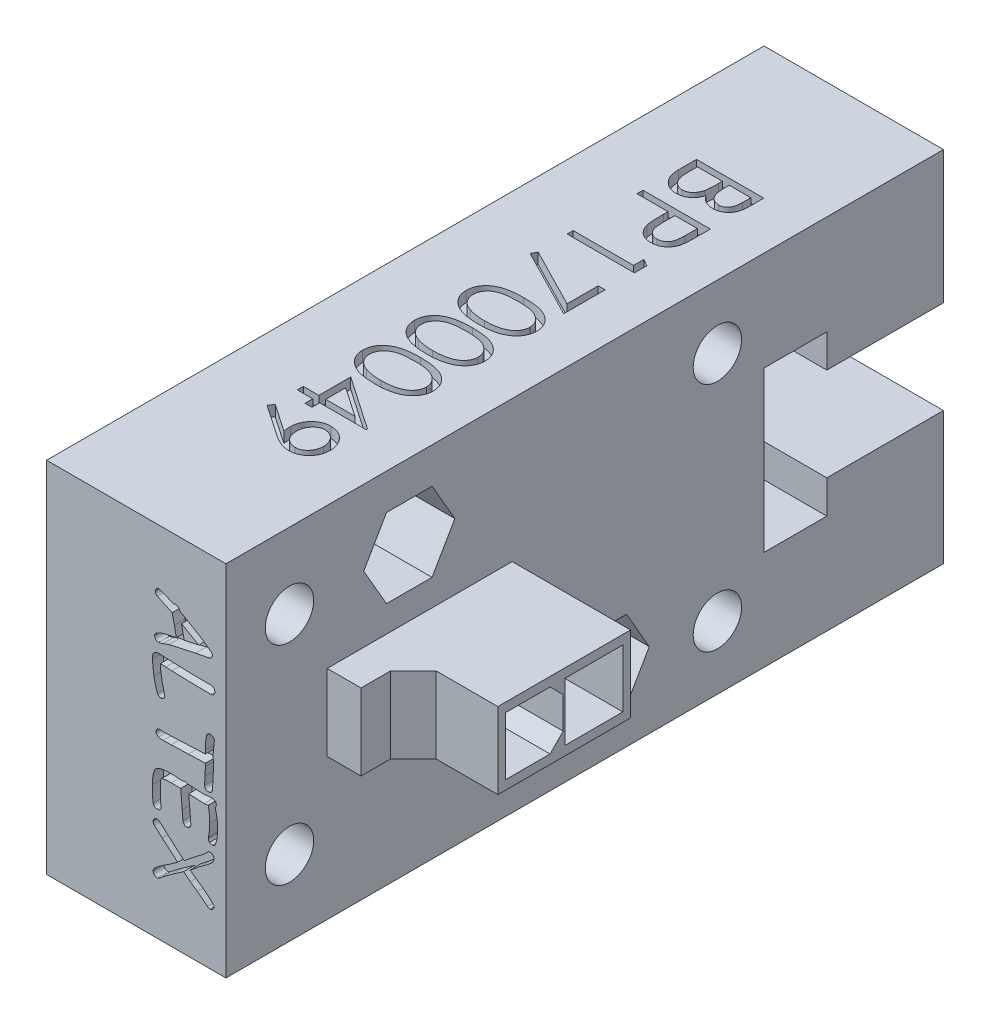
SolidWorks part; units mm, degrees
ref_plane "Front Plane" through (0, 0, 0) normal (1, 0, 0) x (0, 1, 0)
ref_plane "Top Plane" through (0, 0, 0) normal (0, 0, 1) x (0, 1, 0)
ref_plane "Right Plane" through (0, 0, 0) normal (0, 1, 0) x (-1, 0, 0)
sketch "Sketch1" plane through (0, 0, 0) normal (1, 0, 0) x (0, 1, 0)
  line L1 (-12.7, -25.4) -> (12.7, -25.4)
  line L2 (-12.7, -25.4) -> (-12.7, 25.4)
  line L3 (-12.7, 25.4) -> (12.7, 25.4)
  line L4 (12.7, -25.4) -> (12.7, 25.4)
  line L5 (-12.7, -25.4) -> (12.7, 25.4) construction
  line L6 (-12.7, 25.4) -> (12.7, -25.4) construction
  point P0 (0, 0)
  dimension "D1" = 25.4
  dimension "D2" = 50.8
extrude "Boss-Extrude1" add sketch "Sketch1" along normal blind 12.7
sketch "Sketch2" plane through (12.7, 0, 0) normal (1, 0, 0) x (0, 1, 0)
  line L0 (0, -25.4) -> (0, -12.7) construction
  line L1 (-12.7, -25.4) -> (12.7, -25.4) construction
  line L2 (3.302, -17.145) -> (5.6515, -17.145)
  line L3 (-5.6515, -12.7) -> (5.6515, -12.7)
  line L4 (-5.6515, -12.7) -> (-5.6515, -17.145)
  line L5 (-5.6515, -17.145) -> (-3.302, -17.145)
  line L6 (5.6515, -12.7) -> (5.6515, -17.145)
  line L8 (-3.302, -17.145) -> (-3.302, -25.4)
  line L9 (-3.302, -25.4) -> (3.302, -25.4)
  line L10 (3.302, -17.145) -> (3.302, -25.4)
  dimension "D1" = 12.7
  dimension "D2" = 6.604
  dimension "D3" = 3.302
  dimension "D4" = 4.445
  dimension "D5" = 5.6515
  dimension "D6" = 11.303
extrude "Cut-Extrude1" cut sketch "Sketch2" against normal up to vertex (12.7 mm away) up to point (0, 12.7, -25.4)
sketch "Sketch3" plane through (0, 0, 0) normal (-1, 0, 0) x (0, -1, 0)
  circle A0 centre (0, 12.107) radius 1.0287
  circle A1 centre (0, 7.907) radius 1.0287
  dimension "D1" = 2.0574
  dimension "D2" = 2.0574
extrude "Cut-Extrude2" cut sketch "Sketch3" against normal up to vertex (12.7 mm away) up to point (12.7, 12.7, 25.4)
sketch "Sketch6" plane through (0, 0, 25.4) normal (0, 0, 1) x (1, 0, 0)
  line L0 (7.7518, 12.7) -> (7.7518, -12.7) construction
  text T0 "ALTEX" font "Comic Sans MS" height in points 16
extrude "Cut-Extrude4" cut sketch "Sketch6" against normal blind 0.762
sketch "Sketch7" plane through (0, -12.7, 0) normal (0, -1, 0) x (1, 0, 0)
  line L0 (6.35, 25.4) -> (6.35, -25.4) construction
  line L1 (12.7, -25.4) -> (0, -25.4) construction
  line L2 (12.7, 25.4) -> (0, 25.4) construction
  text T0 "39-01-2020" font "Century Gothic" height in points 18
extrude "Cut-Extrude5" cut sketch "Sketch7" against normal blind 0.762
sketch "Sketch8" plane through (0, 12.7, 0) normal (0, 1, 0) x (-1, 0, 0)
  line L0 (-4.5604, -25.4) -> (-4.5604, 25.4) construction
  line L1 (-12.7, -25.4) -> (0, -25.4) construction
  line L2 (-12.7, 25.4) -> (0, 25.4) construction
  text T0 "BP1700049" font "Century Gothic" height in points 18
extrude "Cut-Extrude6" cut sketch "Sketch8" against normal blind 0.762
sketch "Sketch9" plane through (0, 0, 25.4) normal (0, 0, 1) x (1, 0, 0)
  line L0 (1.2659, 12.7) -> (1.2659, -12.7) construction
  line L1 (12.7, 12.7) -> (0, 12.7) construction
  line L2 (12.7, -12.7) -> (0, -12.7) construction
  text T0 "PCHI#10" font "Comic Sans MS" height in points 14
sketch "Sketch10" plane through (12.7, 0, 0) normal (1, 0, 0) x (0, 1, 0)
  line L0 (-12.7, 25.4) -> (-12.7, -25.4) construction
  line L1 (-7.366, 17.6775) -> (-4.572, 19.2907)
  line L2 (-4.572, 19.2907) -> (-4.572, 22.5169)
  line L3 (-4.572, 22.5169) -> (-7.366, 24.13)
  line L4 (-7.366, 24.13) -> (-10.16, 22.5169)
  line L5 (-10.16, 22.5169) -> (-10.16, 19.2907)
  line L6 (-10.16, 19.2907) -> (-7.366, 17.6775)
  line L7 (7.366, 17.6775) -> (10.16, 19.2907)
  line L8 (10.16, 19.2907) -> (10.16, 22.5169)
  line L9 (10.16, 22.5169) -> (7.366, 24.13)
  line L10 (7.366, 24.13) -> (4.572, 22.5169)
  line L11 (4.572, 22.5169) -> (4.572, 19.2907)
  line L12 (4.572, 19.2907) -> (7.366, 17.6775)
  line L13 (12.7, -25.4) -> (12.7, 25.4) construction
  line L14 (12.7, 25.4) -> (-12.7, 25.4) construction
  line L15 (-12.7, -25.4) -> (-3.302, -25.4) construction
  line L16 (-4.9775, -9.398) -> (-6.5907, -6.604)
  line L17 (-6.5907, -6.604) -> (-9.8169, -6.604)
  line L18 (-9.8169, -6.604) -> (-11.43, -9.398)
  line L19 (-11.43, -9.398) -> (-9.8169, -12.192)
  line L20 (-9.8169, -12.192) -> (-6.5907, -12.192)
  line L21 (-6.5907, -12.192) -> (-4.9775, -9.398)
  line L22 (11.43, -9.398) -> (9.8169, -6.604)
  line L23 (9.8169, -6.604) -> (6.5907, -6.604)
  line L24 (6.5907, -6.604) -> (4.9775, -9.398)
  line L25 (4.9775, -9.398) -> (6.5907, -12.192)
  line L26 (6.5907, -12.192) -> (9.8169, -12.192)
  line L27 (9.8169, -12.192) -> (11.43, -9.398)
  circle A0 centre (-7.366, 20.9038) radius 2.794 construction
  circle A1 centre (7.366, 20.9038) radius 2.794 construction
  circle A2 centre (-8.2038, -9.398) radius 2.794 construction
  circle A3 centre (8.2038, -9.398) radius 2.794 construction
  dimension "D1" = 5.588
  dimension "D2" = 5.588
  dimension "D3" = 2.54
  dimension "D4" = 2.54
  dimension "D5" = 1.27
  dimension "D6" = 1.27
  dimension "D7" = 5.588
  dimension "D8" = 5.588
  dimension "D9" = 1.27
  dimension "D10" = 1.27
  dimension "D11" = 13.208
extrude "Cut-Extrude8" cut sketch "Sketch10" against normal blind 2.54
sketch "Sketch11" plane through (0, 0, 0) normal (-1, 0, 0) x (0, -1, 0)
  line L0 (-7.366, 24.13) -> (-7.366, 17.6775) construction
  line L1 (-7.366, 17.6775) -> (7.366, 24.13) construction
  line L2 (7.366, 24.13) -> (7.366, 17.6775) construction
  line L3 (7.366, 17.6775) -> (4.9775, -9.398) construction
  line L4 (4.9775, -9.398) -> (11.43, -9.398) construction
  line L5 (11.43, -9.398) -> (-9.8169, -6.604) construction
  line L6 (-9.8169, -6.604) -> (-6.5907, -12.192) construction
  line L8 (-7.366, 24.13) -> (-10.16, 22.5169)
  line L9 (-10.16, 22.5169) -> (-10.16, 19.2907)
  line L10 (-10.16, 19.2907) -> (-7.366, 17.6775)
  line L11 (-7.366, 17.6775) -> (-4.572, 19.2907)
  line L12 (-4.572, 19.2907) -> (-4.572, 22.5169)
  line L13 (-4.572, 22.5169) -> (-7.366, 24.13)
  line L14 (7.366, 17.6775) -> (10.16, 19.2907)
  line L15 (10.16, 19.2907) -> (10.16, 22.5169)
  line L16 (10.16, 22.5169) -> (7.366, 24.13)
  line L17 (7.366, 24.13) -> (4.572, 22.5169)
  line L18 (4.572, 22.5169) -> (4.572, 19.2907)
  line L19 (4.572, 19.2907) -> (7.366, 17.6775)
  line L20 (11.43, -9.398) -> (9.8169, -6.604)
  line L21 (9.8169, -6.604) -> (6.5907, -6.604)
  line L22 (6.5907, -6.604) -> (4.9775, -9.398)
  line L23 (4.9775, -9.398) -> (6.5907, -12.192)
  line L24 (6.5907, -12.192) -> (9.8169, -12.192)
  line L25 (9.8169, -12.192) -> (11.43, -9.398)
  line L26 (-9.8169, -6.604) -> (-11.43, -9.398)
  line L27 (-11.43, -9.398) -> (-9.8169, -12.192)
  line L28 (-9.8169, -12.192) -> (-6.5907, -12.192)
  line L29 (-6.5907, -12.192) -> (-4.9775, -9.398)
  line L30 (-4.9775, -9.398) -> (-6.5907, -6.604)
  line L31 (-6.5907, -6.604) -> (-9.8169, -6.604)
  circle A0 centre (-8.2038, -9.398) radius 1.651 construction
  circle A1 centre (8.2038, -9.398) radius 1.651 construction
  circle A2 centre (7.366, 20.9038) radius 1.651 construction
  circle A3 centre (-7.366, 20.9038) radius 1.7145 construction
  circle A4 centre (-7.366, 20.9038) radius 2.794 construction
  circle A5 centre (7.366, 20.9038) radius 2.794 construction
  circle A6 centre (8.2038, -9.398) radius 2.794 construction
  circle A7 centre (-8.2038, -9.398) radius 2.794 construction
  dimension "D1" = 3.429
  dimension "D2" = 3.302
extrude "Cut-Extrude9" cut sketch "Sketch11" against normal blind 2.54
sketch "Sketch12" plane through (2.54, 0, 0) normal (-1, 0, 0) x (0, -1, 0)
  line L0 (-7.366, 17.6775) -> (-7.366, 24.13) construction
  line L1 (-7.366, 24.13) -> (7.366, 24.13) construction
  line L2 (7.366, 24.13) -> (7.366, 17.6775) construction
  line L3 (7.366, 17.6775) -> (9.8169, -6.604) construction
  line L4 (9.8169, -6.604) -> (6.5907, -12.192) construction
  line L5 (6.5907, -12.192) -> (-6.5907, -12.192) construction
  line L6 (-6.5907, -12.192) -> (-9.8169, -6.604) construction
  circle A0 centre (-8.2038, -9.398) radius 1.7145
  circle A1 centre (8.2038, -9.398) radius 1.7145
  circle A2 centre (7.366, 20.9038) radius 1.7145
  circle A3 centre (-7.366, 20.9038) radius 1.7145
  dimension "D1" = 3.429
extrude "Cut-Extrude10" cut sketch "Sketch12" against normal up to vertex (7.62 mm away) up to point (10.16, -4.572, 19.2907)
sketch "Sketch13" plane through (12.7, 0, 0) normal (1, 0, 0) x (0, 1, 0)
  line L0 (1.0596, 10.0542) -> (1.9032, 10.8978)
  line L1 (-1.9032, 13.8352) -> (1.9032, 13.8352)
  line L2 (-1.9032, 13.8352) -> (-1.9032, 10.8978)
  line L3 (-1.0596, 10.0542) -> (1.0596, 10.0542)
  line L4 (1.9032, 13.8352) -> (1.9032, 10.8978)
  line L5 (-1.9032, 9.6098) -> (1.9032, 9.6098)
  line L6 (-1.9032, 9.6098) -> (-1.9032, 5.8288)
  line L7 (-1.9032, 5.8288) -> (1.9032, 5.8288)
  line L8 (1.9032, 9.6098) -> (1.9032, 5.8288)
  line L9 (-1.0596, 10.0542) -> (-1.9032, 10.8978)
  line L10 (1.7, 13.632) -> (3.3632, 13.632) construction
  line L11 (1.7, 13.632) -> (1.7, 12.5497) construction
  line L12 (1.7, 13.632) -> (1.7, 10.982) construction
  line L13 (1.7, 9.432) -> (3.2737, 9.432) construction
  line L14 (1.7, 9.432) -> (1.7, 6.7746) construction
  line L15 (1.7, 9.432) -> (1.7, 6.032) construction
  line L16 (0.95, 10.232) -> (2.5714, 10.232) construction
  line L17 (-1.7, 10.982) -> (-1.7, 9.7205) construction
  line L19 (1.7, 6.032) -> (-1.7, 6.032) construction
  line L20 (-7.4385, 14.732) -> (5.1104, 14.732) construction
  line L21 (-3.1732, 14.5288) -> (3.1732, 14.5288)
  line L22 (-3.1732, 14.5288) -> (-3.1732, 5.3238)
  line L23 (-3.1732, 5.3238) -> (3.1732, 5.3238)
  line L24 (3.1732, 14.5288) -> (3.1732, 5.3238)
  line L25 (1.5, 14.732) -> (-1.5, 14.732) construction
  dimension "D1" = 45
  dimension "D2" = 45
  dimension "D3" = 0.2032
  dimension "D4" = 0.1778
  dimension "D5" = 0.2032
  dimension "D6" = 0.1778
  dimension "D7" = 0.2032
  dimension "D8" = 0.2032
  dimension "D9" = 0.2032
  dimension "D10" = 0.2032
  dimension "D11" = 0.2032
  dimension "D12" = 1.27
  dimension "D13" = 1.27
extrude "Boss-Extrude2" add sketch "Sketch13" along normal blind 8.382
sketch "Sketch14" plane through (0, -3.1732, 0) normal (0, -1, 0) x (1, 0, 0)
  line L0 (20.3329, 18.232) -> (13.3, 18.232) construction
  line L1 (28.6, 18.232) -> (16, 18.232) construction
  line L2 (15.3, 17.532) -> (15.3, 12.9236) construction
  line L3 (16.8, 14.732) -> (13.3, 18.232) construction
  line L6 (15.0968, 18.232) -> (12.7, 18.232)
  line L7 (15.0968, 18.232) -> (15.0968, 16.1478)
  line L9 (12.7, 18.232) -> (12.7, 14.5288)
  line L10 (21.082, 14.5288) -> (12.7, 14.5288) construction
  line L11 (16.7158, 14.5288) -> (15.0968, 16.1478)
  line L12 (12.7, 14.5288) -> (16.7158, 14.5288)
  dimension "D1" = 0.2032
  dimension "D2" = 0.2032
extrude "Boss-Extrude3" add sketch "Sketch14" against normal up to vertex (6.3464 mm away) up to point (21.082, 3.1732, 14.5288)
sketch "Sketch15" plane through (21.082, 0, 0) normal (1, 0, 0) x (0, 1, 0)
  line L0 (3.1732, 18.232) -> (-3.1732, 18.232) construction
  line L1 (-3.1732, 5.3238) -> (-2.7, 5.3238)
  line L2 (-3.1732, 5.3238) -> (-3.1732, 18.232)
  line L3 (-3.1732, 18.232) -> (-2.7, 18.232)
  line L4 (-2.7, 5.3238) -> (-2.7, 18.232)
  line L5 (2.7, 9.5624) -> (2.7, 4.4692) construction
  line L6 (2.7, 18.232) -> (3.1732, 18.232)
  line L7 (2.7, 18.232) -> (2.7, 5.3238)
  line L8 (2.7, 5.3238) -> (3.1732, 5.3238)
  line L9 (3.1732, 18.232) -> (3.1732, 5.3238)
  line L10 (2.7, 4.132) -> (2.7, 14.732) construction
  line L11 (-2.7, 9.432) -> (-2.7, 4.4692) construction
  line L12 (-2.7, 4.132) -> (-2.7, 14.732) construction
extrude "Cut-Extrude11" cut sketch "Sketch15" against normal up to vertex (8.382 mm away) up to point (12.7, 12.7, 25.4)
sketch "Sketch16" plane through (21.082, 0, 0) normal (1, 0, 0) x (0, 1, 0)
  line L1 (-2.7, 5.3238) -> (2.7, 5.3238)
  line L2 (-2.7, 5.3238) -> (-2.7, 5.132)
  line L3 (-2.7, 5.132) -> (2.7, 5.132)
  line L4 (2.7, 5.3238) -> (2.7, 5.132)
extrude "Boss-Extrude4" add sketch "Sketch16" against normal up to vertex (8.382 mm away) up to point (12.7, -2.7, 5.3238)
sketch "Sketch17" plane through (12.7, 0, 0) normal (1, 0, 0) x (0, 1, 0)
  line L12 (1.9794, 13.9114) -> (-1.9794, 13.9114)
  line L13 (-1.9794, 13.9114) -> (-1.9794, 10.8663)
  line L14 (-1.9794, 10.8663) -> (-1.0911, 9.978)
  line L15 (-1.0911, 9.978) -> (1.0911, 9.978)
  line L16 (1.0911, 9.978) -> (1.9794, 10.8663)
  line L17 (1.9794, 10.8663) -> (1.9794, 13.9114)
  line L18 (1.9794, 13.9114) -> (-1.9794, 13.9114)
  line L19 (-1.9794, 13.9114) -> (-1.9794, 10.8663)
  line L20 (-1.9794, 10.8663) -> (-1.0911, 9.978)
  line L21 (-1.0911, 9.978) -> (1.0911, 9.978)
  line L22 (1.0911, 9.978) -> (1.9794, 10.8663)
  line L23 (1.9794, 10.8663) -> (1.9794, 13.9114)
  line L26 (1.9794, 9.686) -> (-1.9794, 9.686)
  line L27 (-1.9794, 9.686) -> (-1.9794, 5.7526)
  line L28 (-1.9794, 5.7526) -> (1.9794, 5.7526)
  line L29 (1.9794, 5.7526) -> (1.9794, 9.686)
  line L30 (1.9794, 9.686) -> (-1.9794, 9.686)
  line L31 (-1.9794, 9.686) -> (-1.9794, 5.7526)
  line L32 (-1.9794, 5.7526) -> (1.9794, 5.7526)
  line L33 (1.9794, 5.7526) -> (1.9794, 9.686)
  dimension "D1" = 0.0762
  dimension "D2" = 0.0762
extrude "Cut-Extrude12" cut sketch "Sketch17" along normal up to vertex (8.382 mm away) up to point (21.082, -2.7, 5.132)
sketch "Sketch18" plane through (10.16, 0, 0) normal (1, 0, 0) x (0, 1, 0)
  line L0 (9.8169, -12.192) -> (11.43, -9.398) construction
  line L1 (11.43, -9.398) -> (9.8169, -6.604) construction
  line L2 (9.8169, -6.604) -> (6.5907, -6.604) construction
  line L3 (6.5907, -6.604) -> (4.9775, -9.398) construction
  line L4 (4.9775, -9.398) -> (6.5907, -12.192) construction
  line L5 (6.5907, -12.192) -> (9.8169, -12.192) construction
  line L6 (-10.16, 19.2907) -> (-7.366, 17.6775)
  line L7 (-7.366, 17.6775) -> (-4.572, 19.2907)
  line L8 (-4.572, 19.2907) -> (-4.572, 22.5169)
  line L9 (-4.572, 22.5169) -> (-7.366, 24.13)
  line L10 (-7.366, 24.13) -> (-10.16, 22.5169)
  line L11 (-10.16, 22.5169) -> (-10.16, 19.2907)
  line L12 (-10.16, 19.2907) -> (-7.366, 17.6775)
  line L13 (-7.366, 17.6775) -> (-4.572, 19.2907)
  line L14 (-4.572, 19.2907) -> (-4.572, 22.5169)
  line L15 (-4.572, 22.5169) -> (-7.366, 24.13)
  line L16 (-7.366, 24.13) -> (-10.16, 22.5169)
  line L17 (-10.16, 22.5169) -> (-10.16, 19.2907)
  line L18 (4.572, 19.2907) -> (7.366, 17.6775)
  line L19 (7.366, 17.6775) -> (10.16, 19.2907)
  line L20 (10.16, 19.2907) -> (10.16, 22.5169)
  line L21 (10.16, 22.5169) -> (7.366, 24.13)
  line L22 (7.366, 24.13) -> (4.572, 22.5169)
  line L23 (4.572, 22.5169) -> (4.572, 19.2907)
  line L24 (4.572, 19.2907) -> (7.366, 17.6775)
  line L25 (7.366, 17.6775) -> (10.16, 19.2907)
  line L26 (10.16, 19.2907) -> (10.16, 22.5169)
  line L27 (10.16, 22.5169) -> (7.366, 24.13)
  line L28 (7.366, 24.13) -> (4.572, 22.5169)
  line L29 (4.572, 22.5169) -> (4.572, 19.2907)
  line L30 (-6.5907, -12.192) -> (-4.9775, -9.398) construction
  line L31 (-4.9775, -9.398) -> (-6.5907, -6.604) construction
  line L32 (-6.5907, -6.604) -> (-9.8169, -6.604) construction
  line L33 (-9.8169, -6.604) -> (-11.43, -9.398) construction
  line L34 (-11.43, -9.398) -> (-9.8169, -12.192) construction
  line L35 (-9.8169, -12.192) -> (-6.5907, -12.192) construction
  line L36 (9.8169, -12.192) -> (11.43, -9.398)
  line L37 (11.43, -9.398) -> (9.8169, -6.604)
  line L38 (9.8169, -6.604) -> (6.5907, -6.604)
  line L39 (6.5907, -6.604) -> (4.9775, -9.398)
  line L40 (4.9775, -9.398) -> (6.5907, -12.192)
  line L41 (6.5907, -12.192) -> (9.8169, -12.192)
  line L42 (-6.5907, -12.192) -> (-4.9775, -9.398)
  line L43 (-4.9775, -9.398) -> (-6.5907, -6.604)
  line L44 (-6.5907, -6.604) -> (-9.8169, -6.604)
  line L45 (-9.8169, -6.604) -> (-11.43, -9.398)
  line L46 (-11.43, -9.398) -> (-9.8169, -12.192)
  line L47 (-9.8169, -12.192) -> (-6.5907, -12.192)
  circle A2 centre (-8.2038, -9.398) radius 1.7145 construction
  circle A3 centre (8.2038, -9.398) radius 1.7145 construction
  circle A4 centre (-8.2038, -9.398) radius 1.7145
  circle A5 centre (8.2038, -9.398) radius 1.7145
  circle A6 centre (7.366, 20.9038) radius 1.7145 construction
  circle A7 centre (-7.366, 20.9038) radius 1.7145 construction
  circle A8 centre (7.366, 20.9038) radius 1.7145
  circle A9 centre (-7.366, 20.9038) radius 1.7145
  dimension "D1" = 0
  dimension "D2" = 0
extrude "Boss-Extrude6" add sketch "Sketch18" along normal up to vertex up to point (12.7, -12.7, 25.4)
sketch "Sketch19" plane through (2.54, 0, 0) normal (-1, 0, 0) x (0, -1, 0)
  line L0 (4.9775, -9.398) -> (6.5907, -12.192) construction
  line L1 (6.5907, -12.192) -> (9.8169, -12.192) construction
  line L2 (9.8169, -12.192) -> (11.43, -9.398) construction
  line L3 (11.43, -9.398) -> (9.8169, -6.604) construction
  line L4 (9.8169, -6.604) -> (6.5907, -6.604) construction
  line L5 (6.5907, -6.604) -> (4.9775, -9.398) construction
  line L6 (-6.5907, -6.604) -> (-9.8169, -6.604) construction
  line L7 (-9.8169, -6.604) -> (-11.43, -9.398) construction
  line L8 (-11.43, -9.398) -> (-9.8169, -12.192) construction
  line L9 (-9.8169, -12.192) -> (-6.5907, -12.192) construction
  line L10 (-6.5907, -12.192) -> (-4.9775, -9.398) construction
  line L11 (-4.9775, -9.398) -> (-6.5907, -6.604) construction
  line L12 (-4.572, 22.5169) -> (-7.366, 24.13) construction
  line L13 (-7.366, 24.13) -> (-10.16, 22.5169) construction
  line L14 (-10.16, 22.5169) -> (-10.16, 19.2907) construction
  line L15 (-10.16, 19.2907) -> (-7.366, 17.6775) construction
  line L16 (-7.366, 17.6775) -> (-4.572, 19.2907) construction
  line L17 (-4.572, 19.2907) -> (-4.572, 22.5169) construction
  line L18 (7.366, 24.13) -> (4.572, 22.5169) construction
  line L19 (4.572, 22.5169) -> (4.572, 19.2907) construction
  line L20 (4.572, 19.2907) -> (7.366, 17.6775) construction
  line L21 (7.366, 17.6775) -> (10.16, 19.2907) construction
  line L22 (10.16, 19.2907) -> (10.16, 22.5169) construction
  line L23 (10.16, 22.5169) -> (7.366, 24.13) construction
  line L24 (4.9775, -9.398) -> (6.5907, -12.192)
  line L25 (6.5907, -12.192) -> (9.8169, -12.192)
  line L26 (9.8169, -12.192) -> (11.43, -9.398)
  line L27 (11.43, -9.398) -> (9.8169, -6.604)
  line L28 (9.8169, -6.604) -> (6.5907, -6.604)
  line L29 (6.5907, -6.604) -> (4.9775, -9.398)
  line L30 (-6.5907, -6.604) -> (-9.8169, -6.604)
  line L31 (-9.8169, -6.604) -> (-11.43, -9.398)
  line L32 (-11.43, -9.398) -> (-9.8169, -12.192)
  line L33 (-9.8169, -12.192) -> (-6.5907, -12.192)
  line L34 (-6.5907, -12.192) -> (-4.9775, -9.398)
  line L35 (-4.9775, -9.398) -> (-6.5907, -6.604)
  line L36 (-4.572, 22.5169) -> (-7.366, 24.13)
  line L37 (-7.366, 24.13) -> (-10.16, 22.5169)
  line L38 (-10.16, 22.5169) -> (-10.16, 19.2907)
  line L39 (-10.16, 19.2907) -> (-7.366, 17.6775)
  line L40 (-7.366, 17.6775) -> (-4.572, 19.2907)
  line L41 (-4.572, 19.2907) -> (-4.572, 22.5169)
  line L42 (7.366, 24.13) -> (4.572, 22.5169)
  line L43 (4.572, 22.5169) -> (4.572, 19.2907)
  line L44 (4.572, 19.2907) -> (7.366, 17.6775)
  line L45 (7.366, 17.6775) -> (10.16, 19.2907)
  line L46 (10.16, 19.2907) -> (10.16, 22.5169)
  line L47 (10.16, 22.5169) -> (7.366, 24.13)
extrude "Cut-Extrude13" cut sketch "Sketch19" against normal blind 7.112
sketch "Sketch20" plane through (12.7, 0, 0) normal (1, 0, 0) x (0, 1, 0)
  line L0 (-7.366, 17.6775) -> (-7.366, -4.572) construction
  line L2 (7.366, 17.6775) -> (7.366, -6.604) construction
  line L3 (6.5907, -6.604) -> (9.8169, -6.604) construction
  line L4 (-9.0868, -6.604) -> (8.8237, -6.604) construction
  line L5 (-7.366, 1.8805) -> (-10.16, 0.2673)
  line L6 (-10.16, 0.2673) -> (-10.16, -2.9589)
  line L7 (-10.16, -2.9589) -> (-7.366, -4.572)
  line L8 (-7.366, -4.572) -> (-4.572, -2.9589)
  line L9 (-4.572, -2.9589) -> (-4.572, 0.2673)
  line L10 (-4.572, 0.2673) -> (-7.366, 1.8805)
  line L11 (7.366, 9.1931) -> (10.16, 10.8062)
  line L12 (10.16, 10.8062) -> (10.16, 14.0324)
  line L13 (10.16, 14.0324) -> (7.366, 15.6455)
  line L14 (7.366, 15.6455) -> (4.572, 14.0324)
  line L15 (4.572, 14.0324) -> (4.572, 10.8062)
  line L16 (4.572, 10.8062) -> (7.366, 9.1931)
  line L17 (-9.8169, -6.604) -> (-6.5907, -6.604) construction
  circle A0 centre (-7.366, -1.3458) radius 2.794 construction
  circle A1 centre (7.366, 12.4193) radius 2.794 construction
  dimension "D1" = 5.588
  dimension "D2" = 5.588
  dimension "D3" = 2.032
  dimension "D4" = 2.032
extrude "Cut-Extrude14" cut sketch "Sketch20" against normal blind 10.414
sketch "Sketch21" plane through (2.286, 0, 0) normal (1, 0, 0) x (0, 1, 0)
  line L0 (-10.16, 0.2673) -> (-4.572, -2.9589) construction
  line L1 (-4.572, -2.9589) -> (7.366, 9.1931) construction
  line L2 (7.366, 9.1931) -> (7.366, 15.6455) construction
  circle A0 centre (7.366, 12.4193) radius 1.651
  circle A1 centre (-7.366, -1.3458) radius 1.651
  dimension "D1" = 3.302
  dimension "D2" = 3.302
extrude "Cut-Extrude15" cut sketch "Sketch21" against normal up to vertex up to point (0, -12.7, 25.4)
sketch "Sketch23" plane through (21.082, 0, 0) normal (1, 0, 0) x (0, 1, 0)
  line L0 (2.0556, 10.8347) -> (2.0556, 13.9876)
  line L1 (2.0556, 13.9876) -> (-2.0556, 13.9876)
  line L2 (-2.0556, 13.9876) -> (-2.0556, 10.8347)
  line L3 (-2.0556, 10.8347) -> (-1.1227, 9.9018)
  line L4 (1.9794, 5.7526) -> (1.9794, 9.686)
  line L5 (1.9794, 9.686) -> (-1.9794, 9.686)
  line L6 (-1.9794, 9.686) -> (-1.9794, 5.7526)
  line L7 (-1.9794, 5.7526) -> (1.9794, 5.7526)
  line L8 (1.9794, 5.7526) -> (1.9794, 9.686)
  line L9 (1.9794, 9.686) -> (-1.9794, 9.686)
  line L10 (-1.9794, 9.686) -> (-1.9794, 5.7526)
  line L11 (-1.9794, 5.7526) -> (1.9794, 5.7526)
  line L12 (-1.1227, 9.9018) -> (1.1227, 9.9018)
  line L13 (1.1227, 9.9018) -> (2.0556, 10.8347)
  line L14 (1.9794, 10.8663) -> (1.9794, 13.9114)
  line L15 (1.9794, 13.9114) -> (-1.9794, 13.9114)
  line L16 (-1.9794, 13.9114) -> (-1.9794, 10.8663)
  line L17 (-1.9794, 10.8663) -> (-1.0911, 9.978)
  line L18 (-1.0911, 9.978) -> (1.0911, 9.978)
  line L19 (1.0911, 9.978) -> (1.9794, 10.8663)
  line L20 (1.9794, 10.8663) -> (1.9794, 13.9114)
  line L21 (1.9794, 13.9114) -> (-1.9794, 13.9114)
  line L22 (-1.9794, 13.9114) -> (-1.9794, 10.8663)
  line L23 (-1.9794, 10.8663) -> (-1.0911, 9.978)
  line L24 (-1.0911, 9.978) -> (1.0911, 9.978)
  line L25 (1.0911, 9.978) -> (1.9794, 10.8663)
  line L26 (2.0556, 5.6764) -> (2.0556, 9.7622)
  line L27 (2.0556, 9.7622) -> (-2.0556, 9.7622)
  line L28 (-2.0556, 9.7622) -> (-2.0556, 5.6764)
  line L29 (-2.0556, 5.6764) -> (2.0556, 5.6764)
  dimension "D1" = 0
  dimension "D2" = 0
  dimension "D3" = 0.0762
extrude "Cut-Extrude19" cut sketch "Sketch23" against normal blind 8.382
